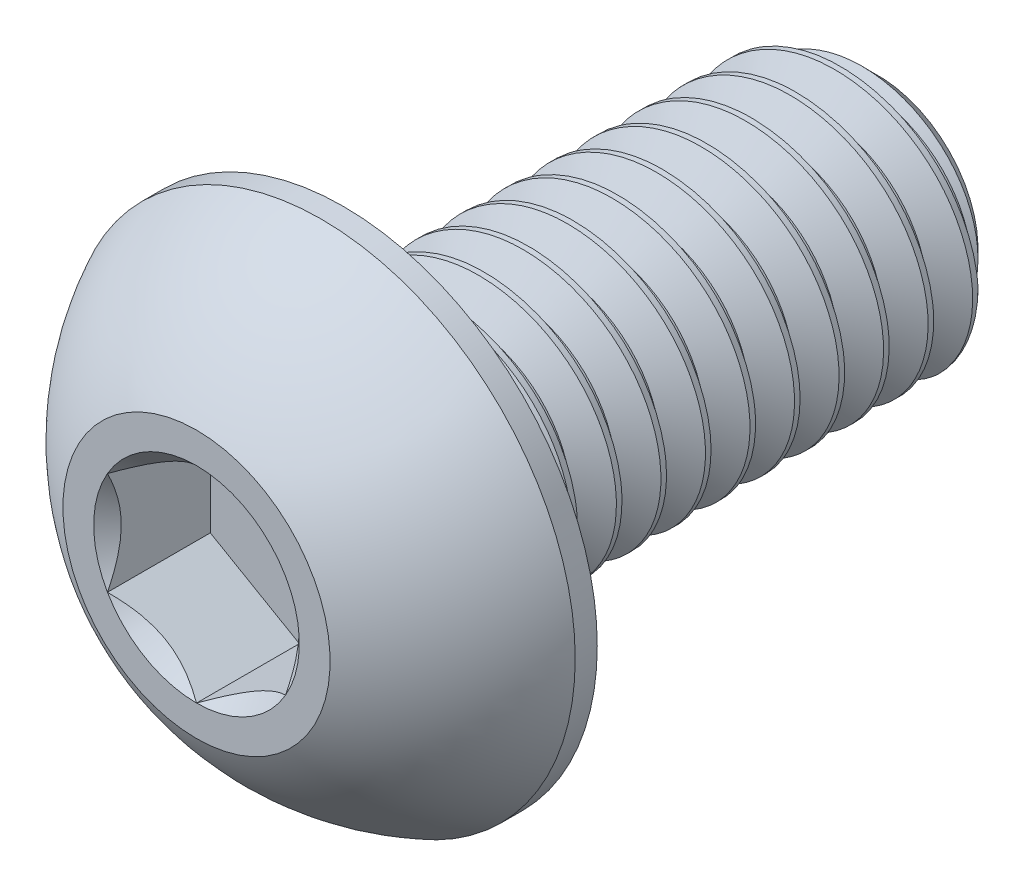
SolidWorks part; units mm, degrees
ref_plane "Front" through (0, 0, 0) normal (0, 0, 1) x (1, 0, 0)
ref_plane "Top" through (0, 0, 0) normal (0, 1, 0) x (1, 0, 0)
ref_plane "Right" through (0, 0, 0) normal (1, 0, 0) x (0, 0, -1)
sketch "Sketch1" plane through (0, 0, 0) normal (1, 0, 0) x (0, 0, -1)
  line L2 (-3, 1.5) -> (3, 1.5)
  line L3 (3, 1.5) -> (3, 0)
  line L4 (3, 0) -> (-3, 0)
  line L6 (-3.2475, 2.85) -> (-3, 2.85) construction
  line L7 (3, 1.5) -> (3, -1.5) construction
  line L8 (-4.65, 0) -> (-3, 0) construction
  line L9 (-3, 2.85) -> (-3, -2.85) construction
  line L11 (-3, 1.5) -> (-3, 0)
  line L13 (-4.65, 1) -> (-4.65, -1) construction
  line L14 (-4.65, 1) -> (-4.65, 1.5) construction
  line L15 (2.9688, 1.5541) -> (3.2188, 1.1211) construction
  line L16 (3.2188, 1.1211) -> (3.4688, 1.5541) construction
  line L17 (3.4688, 1.5541) -> (2.9688, 1.5541) construction
  line L18 (3, 1.5) -> (3.4375, 1.5) construction
  line L19 (3.2188, 1.5541) -> (3.2188, 1.5) construction
  line L20 (3.2188, 1.5) -> (3.2188, 1.1752) construction
  line L21 (3.2188, 1.1752) -> (3.2188, 1.1211) construction
  line L22 (3.1875, 1.1752) -> (3.25, 1.1752)
  line L23 (2.9844, 1.5271) -> (3.4531, 1.5271)
  line L24 (3.25, 1.1752) -> (3.4531, 1.5271)
  line L25 (3.1875, 1.1752) -> (2.9844, 1.5271)
  line L26 (2.625, 1.5) -> (3, 1.125)
  arc A3 (-4.65, 1.5) -> (-3.2475, 2.85) centre (-1.8552, 0) cw construction
  point P29 (3.2188, 1.5271)
  point P30 (1.75, -1.5)
  point P33 (0, 0)
  dimension "Thread Size" = 3
  dimension "D1" = 0.2475
  dimension "Head Height" = 1.65
  dimension "Head Diameter" = 5.7
  dimension "Length" = 6
  dimension "Drive Size" = 2
  dimension "Thread Pitch" = 0.5
  dimension "D3" = 0.0625
  dimension "D2" = 0.375
  dimension "D4" = 45
  dimension "D5" = 1.25
sketch "Sketch10" plane through (0, 0, 0) normal (1, 0, 0) x (0, 0, -1)
  line L0 (2.625, 1.5) -> (3, 1.125) construction
  line L1 (2.625, 1.5) -> (3, 1.125)
  line L4 (3, 1.5) -> (-3, 1.5)
  line L5 (3, 0) -> (3, 1.5)
  line L6 (-3, 0) -> (3, 0)
  line L7 (-3, 1.5) -> (-3, 0)
  line L8 (2.625, 1.5) -> (-3, 1.5)
  line L9 (3, 0) -> (3, 1.125)
  line L10 (-3, 0) -> (3, 0)
  line L11 (-3, 1.5) -> (-3, 0)
  dimension "D1" = 0
revolve "Revolve3" add sketch "Sketch10" angle 360 about L8
sketch "Sketch7" plane through (0, 0, 0) normal (1, 0, 0) x (0, 0, -1)
  line L6 (-3.2475, 2.85) -> (-3, 2.85) construction
  line L8 (-4.65, 0) -> (-3, 0) construction
  line L11 (-3, 2.85) -> (-3, -2.85) construction
  line L12 (-3.2475, 2.85) -> (-3, 2.85)
  line L13 (-4.65, 0) -> (-3, 0)
  line L14 (-4.65, 1) -> (-4.65, -1) construction
  line L15 (-3, 2.85) -> (-3, 0)
  line L16 (-4.65, 1.5) -> (-4.65, 0)
  arc A2 (-3.2475, 2.85) -> (-4.65, 1.5) centre (-1.8552, 0) ccw construction
  arc A3 (-3.2475, 2.85) -> (-4.65, 1.5) centre (-1.8552, 0) ccw
revolve "Revolve2" add sketch "Sketch7" angle 360 mid plane about L13
sketch "Sketch5" plane through (0, 0, 4.65) normal (0, 0, 1) x (1, 0, 0)
  line L1 (1, -0.5774) -> (1, 0.5774)
  line L2 (1, 0.5774) -> (0, 1.1547)
  line L3 (0, 1.1547) -> (-1, 0.5774)
  line L4 (-1, 0.5774) -> (-1, -0.5774)
  line L5 (-1, -0.5774) -> (0, -1.1547)
  line L6 (0, -1.1547) -> (1, -0.5774)
  circle A0 centre (0, 0) radius 1 construction
extrude "Cut-Extrude2" cut sketch "Sketch5" against normal blind 1.155
sketch "Sketch6" plane through (0, 0, 4.65) normal (0, 0, 1) x (1, 0, 0)
  circle A0 centre (0, 0) radius 1.1547
extrude "Cut-Extrude3" cut sketch "Sketch6" against normal blind 1.155 draft 45
sketch "Sketch9" plane through (0, 0, 3) normal (0, 0, -1) x (-1, 0, 0)
  circle A0 centre (0, 0) radius 1.5 construction
  circle A4 centre (0, 0) radius 1.5
split "Split1" bodies to split 113 resulting bodies 123 124 split by face at (0, -2.85, 3)
sketch "Sketch11" plane through (0, 0, -3) normal (0, 0, -1) x (-1, 0, 0)
  circle A0 centre (0, 0) radius 1.5 construction
  circle A1 centre (0, 0) radius 1.5
curve "Helix/Spiral1" pitch 0.5 height 7.65 radius 1.5 centre (0, 0, -3) axis (0, 0, 1) start towards (0, 1, 0)
sketch "Sketch12" plane through (0, 0, 0) normal (1, 0, 0) x (0, 0, -1)
  line L0 (3.1875, 1.1752) -> (3.25, 1.1752) construction
  line L1 (3.25, 1.1752) -> (3.4531, 1.5271) construction
  line L2 (2.9844, 1.5271) -> (3.4531, 1.5271) construction
  line L3 (3.1875, 1.1752) -> (2.9844, 1.5271) construction
  line L4 (3.1875, 1.1752) -> (3.25, 1.1752)
  line L5 (3.25, 1.1752) -> (3.4531, 1.5271)
  line L6 (2.9844, 1.5271) -> (3.4531, 1.5271)
  line L7 (3.1875, 1.1752) -> (2.9844, 1.5271)
sweep "Cut-Sweep2" cut profiles "Sketch12" path "Helix/Spiral1" align with end faces yes
extrude "Boss-Extrude1" add sketch "Sketch9" along normal blind 10 draft 45
equation "\"D1@Cut-Extrude2\" = \"Head Height@Sketch1\" * .7"
equation "\"D1@Sketch1\" = \"Head Height@Sketch1\" * .15"
equation "\"D1@Cut-Extrude3\" = \"D1@Cut-Extrude2\""
equation "\"D3@Sketch1\" = \"Thread Pitch@Sketch1\" / 8"
equation "\"D2@Sketch1\" = \"Thread Pitch@Sketch1\" * 0.75"
equation "\"D3@Helix/Spiral1\" = \"Length@Sketch1\" + \"Head Height@Sketch1\""
equation "\"D4@Helix/Spiral1\" = \"Thread Pitch@Sketch1\""
equation "\"D5@Sketch1\" = \"Thread Pitch@Sketch1\" * 2.5"
